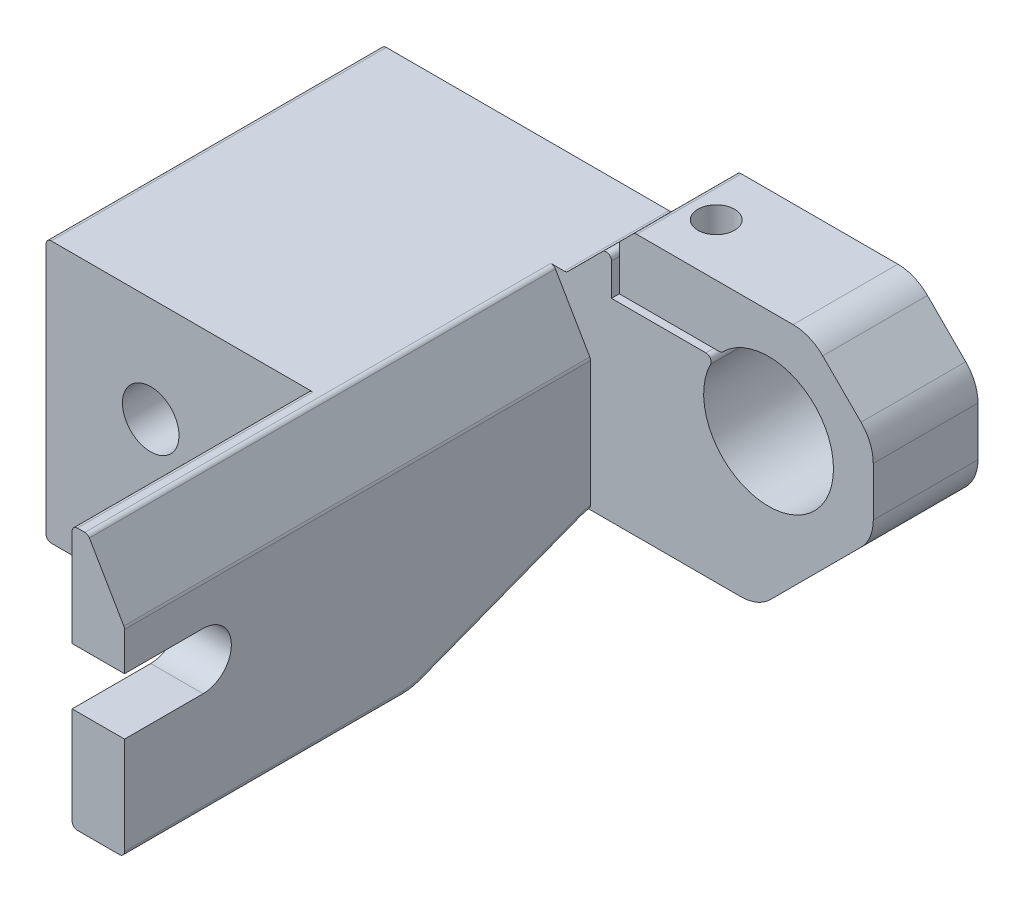
SolidWorks part; units mm, degrees
ref_plane "XY" through (0, 0, 0) normal (0, 0, 1) x (1, 0, 0)
ref_plane "XZ" through (0, 0, 0) normal (0, 1, 0) x (1, 0, 0)
ref_plane "YZ" through (0, 0, 0) normal (1, 0, 0) x (0, 0, -1)
sketch "Sketch1" plane through (0, 0, 0) normal (0, 0, 1) x (1, 0, 0)
  line L0 (-22.5, 15.75) -> (-28.5, 9.75)
  line L1 (-28.5, -9.25) -> (-17.5, -9.25) construction
  line L2 (-28.5, -9.25) -> (-28.5, 1.75) construction
  line L3 (-28.5, 9.25) -> (0.8, 9.25) construction
  line L4 (28.5, -9.25) -> (28.5, 9.25)
  line L5 (-28.5, -9.25) -> (28.5, 9.25) construction
  line L6 (-28.5, 9.25) -> (28.5, -9.25) construction
  line L7 (28.5, -15.75) -> (-28.5, -15.75) construction
  line L8 (28.5, -15.75) -> (28.5, 15.75) construction
  line L9 (28.5, 15.75) -> (-28.5, 15.75) construction
  line L10 (-28.5, -15.75) -> (-28.5, 15.75) construction
  line L11 (28.5, -15.75) -> (-28.5, 15.75) construction
  line L12 (28.5, 15.75) -> (-28.5, -15.75) construction
  line L13 (-5.7, 15.75) -> (-4.25, 14.3)
  line L14 (-5.7, 15.75) -> (-22.5, 15.75)
  line L15 (-17.5, -9.25) -> (-28.5, 1.75)
  line L16 (0.8, 9.25) -> (28.5, 9.25)
  line L17 (-28.5, 9.75) -> (-28.5, 9.25)
  line L18 (-28.5, 1.75) -> (-28.5, 9.25)
  line L19 (-17.5, -9.25) -> (28.5, -9.25)
  line L20 (-13.3824, 9.25) -> (-3.5, 9.25)
  line L21 (-3.5, 9.25) -> (-3.5, 13.55)
  line L22 (-13.9859, 10) -> (-4.25, 10)
  line L23 (-4.25, 10) -> (-4.25, 14.3)
  line L24 (-4.25, 10) -> (-4.25, 13.55) construction
  line L25 (-13.3824, 10) -> (-4.25, 10) construction
  line L26 (-3.5, 13.55) -> (0.8, 9.25)
  line L27 (-4.25, 14.3) -> (-3.5, 13.55) construction
  arc A0 (-13.9859, 10) -> (-13.3824, 9.25) centre (-18.5, 5.75) ccw
  arc A1 (-13.3824, 9.25) -> (-13.9859, 10) centre (-18.5, 5.75) ccw construction
  point P0 (0, 0)
  point P5 (0, 0)
  dimension "D10" = 18.5
  dimension "D12" = 12.4
  dimension "D1" = 57
  dimension "D2" = 18.5
  dimension "D3" = 31.5
  dimension "D4" = 45
  dimension "D5" = 6
  dimension "D6" = 45
  dimension "D7" = 45
  dimension "D8" = 22.8
  dimension "D9" = 11
  dimension "D11" = 5.75
  dimension "D13" = 3.5
  dimension "D14" = 0.75
extrude "Boss-Extrude1" add sketch "Sketch1" along normal blind 10
sketch "Sketch2" plane through (28.5, 0, 0) normal (1, 0, 0) x (0, 0, -1)
  line L0 (-10, 9.25) -> (-10, -9.25)
  line L1 (-10, -9.25) -> (-26.9331, -15.75)
  line L2 (-26.9331, -15.75) -> (-32, -15.75)
  line L3 (-32, -15.75) -> (-32, 9.25)
  line L4 (-32, 9.25) -> (-10, 9.25)
  dimension "D1" = 22
  dimension "D2" = 6.5
  dimension "D3" = 159
extrude "Boss-Extrude2" add sketch "Sketch2" against normal blind 30
sketch "Sketch3" plane through (0, 0, 32) normal (0, 0, 1) x (1, 0, 0)
  line L0 (-1.5, -15.75) -> (28.5, -15.75) construction
  line L1 (-1.5, 9.25) -> (3.5, 9.25)
  line L2 (-1.5, 9.25) -> (-1.5, -15.75)
  line L3 (-1.5, -15.75) -> (3.5, -15.75)
  line L4 (3.5, 9.25) -> (3.5, -15.75)
  dimension "D1" = 5
extrude "Boss-Extrude3" add sketch "Sketch3" along normal blind 22.5
sketch "Sketch4" plane through (0, 0, 0) normal (0, 0, -1) x (-1, 0, 0)
  circle A0 centre (-18.5, -0.75) radius 5.25
  dimension "D1" = 0.75
  dimension "D3" = 10.5
  dimension "D2" = 18.5
extrude "Cut-Extrude1" cut sketch "Sketch4" against normal blind 27
sketch "Sketch5" plane through (0, 0, 32) normal (0, 0, 1) x (1, 0, 0)
  circle A0 centre (18.5, -0.75) radius 2.7
  dimension "D1" = 5.4
extrude "Cut-Extrude3" cut sketch "Sketch5" against normal offset from surface (4.6 mm away) 0.4 up to face at (13.25, -0.75, 27)
sketch "Sketch6" plane through (0, 0, 54.5) normal (0, 0, 1) x (1, 0, 0)
  line L0 (-1.5, 9.25) -> (2, 9.25)
  line L1 (3.5, 9.25) -> (-1.5, 9.25) construction
  line L2 (2, 9.25) -> (-1.5, 3.25)
  line L3 (-1.5, 9.25) -> (-1.5, -15.75) construction
  line L4 (-1.5, 3.25) -> (-1.5, 9.25)
  dimension "D1" = 3.5
  dimension "D2" = 6
extrude "Cut-Extrude4" cut sketch "Sketch6" against normal up to surface (44.5 mm away) up to face at (-11.7439, 6.442, 10)
sketch "Sketch7" plane through (3.5, 0, 0) normal (1, 0, 0) x (0, 0, -1)
  line L0 (-47, -5.95) -> (-54.5, -5.95)
  line L1 (-54.5, -15.75) -> (-54.5, 9.25) construction
  line L2 (-54.5, -5.95) -> (-54.5, -0.55)
  line L3 (-54.5, -0.55) -> (-47, -0.55)
  arc A0 (-47, -5.95) -> (-47, -0.55) centre (-47, -3.25) ccw
  dimension "D1" = 3.25
  dimension "D2" = 47
  dimension "D3" = 5.4
extrude "Cut-Extrude5" cut sketch "Sketch7" against normal up to next
fillet "Fillet1" radius 4 4 edges at (-17.5, -9.25, 5) (-28.5, 1.75, 5) (-28.5, 9.75, 5) (-22.5, 15.75, 5)
fillet "Fillet2" radius 0.5 11 edges at (-1.5, 3.25, 32.25) (2, 9.25, 32.25) (-13.9859, 10, 5) (-13.3824, 9.25, 5) (-3.5, 13.55, 5) (-4.25, 14.3, 5) (28.5, 9.25, 16) (-5.7, 15.75, 5)
fillet "Fillet3" radius 5 2 edges at (13.5, -15.75, 26.9331)
fillet "Fillet4" radius 0.5 9 edges at (28.5, -15.75, 29.9299) (28.5, -15.6663, 26.9486) (28.5, -9.25, 4.5367) (28.5, -9.3337, 9.9845) (-1.5, -9.3337, 9.9845) (-1.5, -15.6663, 26.9486) (28.5, -12.5, 18.4665) (-1.5, -15.75, 41.1799)
ref_plane "Plane1" through (0, 0, 5) normal (0, 0, 1) x (1, 0, 0)
sketch "Sketch8" plane through (0, 0, 5) normal (0, 0, 1) x (1, 0, 0)
  line L0 (-8.5, 24.8529) -> (-8.5, -25.6111) construction
  line L1 (-8.5, 15.75) -> (-6.75, 15.75)
  line L2 (-5.9071, 15.75) -> (-20.8431, 15.75) construction
  line L3 (-6.75, 15.75) -> (-6.75, -4.25)
  line L4 (-6.75, -4.25) -> (-6.15, -4.25)
  line L5 (-6.15, -4.25) -> (-6.15, -8.75)
  line L6 (-6.15, -8.75) -> (-6, -8.75)
  line L7 (-6, -8.75) -> (-6, -9.25)
  line L8 (-15.8431, -9.25) -> (-1.2791, -9.25) construction
  line L9 (-6, -9.25) -> (-8.5, -9.25)
  line L10 (-8.5, -9.25) -> (-8.5, 15.75)
  dimension "D1" = 8.5
  dimension "D2" = 1.75
  dimension "D3" = 20
  dimension "D4" = 0.5
  dimension "D5" = 2.35
  dimension "D6" = 2.5
revolve "Cut-Revolve1" cut sketch "Sketch8" angle 360 about L0
mirror "Mirror1" about plane through (0, 0, 0) normal (1, 0, 0) of bodies 125
delete or keep bodies "Body-Delete1" type delete bodies bodies 125
